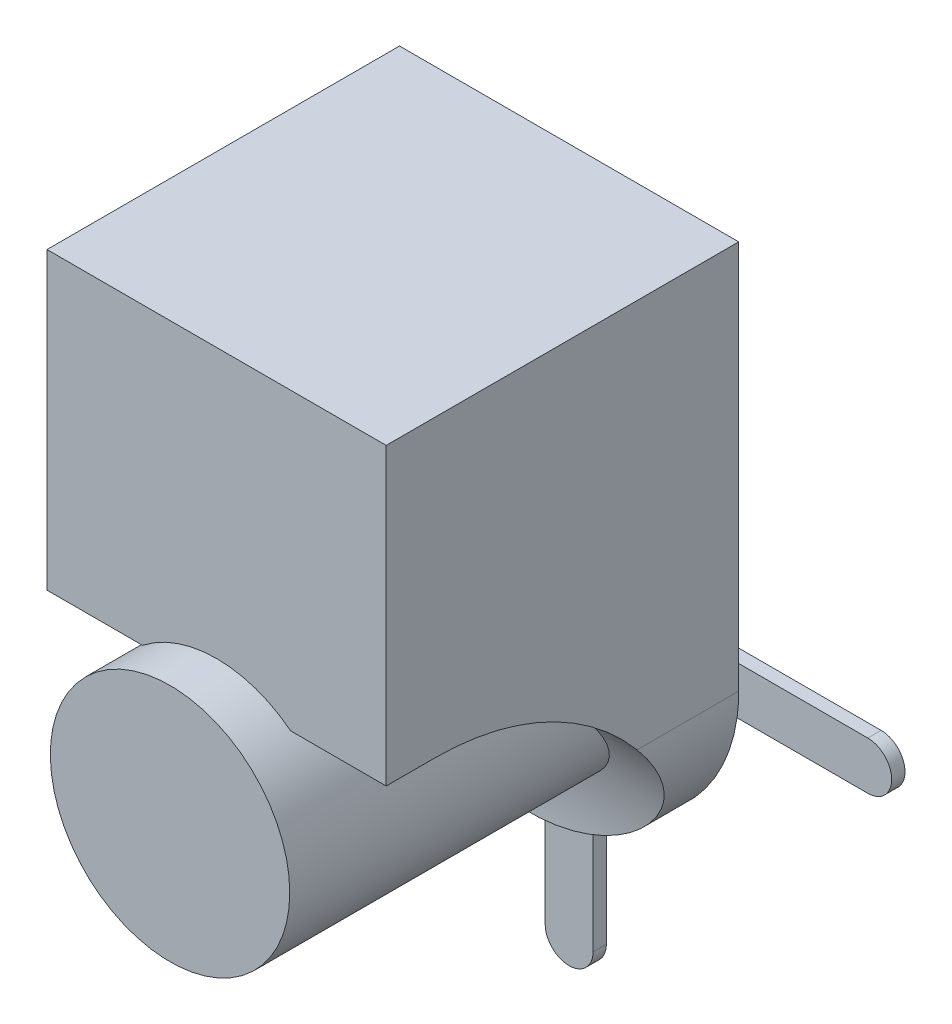
SolidWorks part; units mm, degrees
ref_plane "Front Plane" through (0, 0, 0) normal (0, 0, 1) x (1, 0, 0)
ref_plane "Top Plane" through (0, 0, 0) normal (0, 1, 0) x (1, 0, 0)
ref_plane "Right Plane" through (0, 0, 0) normal (1, 0, 0) x (0, 0, -1)
sketch "Sketch2" plane through (0, 0, 0) normal (0, 0, 1) x (1, 0, 0)
  circle A0 centre (0, 0) radius 18
  dimension "D1" = 36
extrude "Boss-Extrude1" add sketch "Sketch2" along normal blind 60 contours A0
sketch "Sketch3" plane through (0, 0, 0) normal (0, 0, 1) x (1, 0, 0)
  line L1 (-25.5, 0) -> (-25.5, 58.5)
  line L2 (-25.5, 58.5) -> (25.5, 58.5)
  line L3 (25.5, 58.5) -> (25.5, 0)
  arc A0 (-25.5, 0) -> (25.5, 0) centre (0, 0) ccw
  dimension "D1" = 51
extrude "Boss-Extrude2" add sketch "Sketch3" along normal blind 53
sketch "Sketch4" plane through (0, 0, 0) normal (0, 0, 1) x (1, 0, 0)
  line L1 (-3.6, 19.0274) -> (-19.0274, 3.6)
  line L3 (-3.6, -19.0274) -> (-19.0274, -3.6)
  line L4 (3.6, -19.0274) -> (19.0274, -3.6)
  line L5 (3.6, 19.0274) -> (19.0274, 3.6)
  line L6 (3.6, 19.0274) -> (3.6, 44.9)
  line L7 (44.9, 3.6) -> (19.0274, 3.6)
  line L8 (44.9, -3.6) -> (19.0274, -3.6)
  line L9 (-19.0274, 3.6) -> (-44.9, 3.6)
  line L10 (-3.6, 19.0274) -> (-3.6, 44.9)
  line L11 (-19.0274, -3.6) -> (-44.9, -3.6)
  line L14 (3.6, -44.9) -> (3.6, -19.0274)
  line L15 (-3.6, -44.9) -> (-3.6, -19.0274)
  arc A0 (-44.9, 3.6) -> (-44.9, -3.6) centre (-44.9, 0) ccw
  arc A1 (44.9, 3.6) -> (44.9, -3.6) centre (44.9, 0) cw
  arc A2 (-3.6, 44.9) -> (3.6, 44.9) centre (0, 44.9) cw
  arc A3 (-3.6, -44.9) -> (3.6, -44.9) centre (0, -44.9) ccw
  point P0 (-3.6, 19.0274)
  point P2 (3.6, 19.0274)
  point P6 (19.0274, 3.6)
  point P8 (19.0274, -3.6)
  point P9 (3.6, -19.0274)
  point P10 (-3.6, -19.0274)
  point P12 (-19.0274, -3.6)
  point P17 (-19.0274, 3.6)
extrude "Boss-Extrude3" add sketch "Sketch4" against normal blind 2
sketch "Sketch5" plane through (0, 0, 0) normal (1, 0, 0) x (0, 0, -1)
  line L0 (-53, 18) -> (-53, -18) construction
  line L5 (-53, 14.1473) -> (-45.6473, 14.1473)
  line L6 (-53, 14.1473) -> (-53, -25.5)
  line L7 (-53, -25.5) -> (-6, -25.5)
  arc A1 (-6, -25.5) -> (-45.6473, 14.1473) centre (-45.6473, -25.5) ccw
extrude "Cut-Extrude3" cut sketch "Sketch5" against normal through all both and the other way through all
sketch "Sketch6" plane through (0, 0, 60) normal (0, 0, 1) x (1, 0, 0)
  circle A0 centre (0, 0) radius 18 construction
  circle A1 centre (0, 0) radius 18
extrude "Boss-Extrude4" add sketch "Sketch6" against normal blind 56
